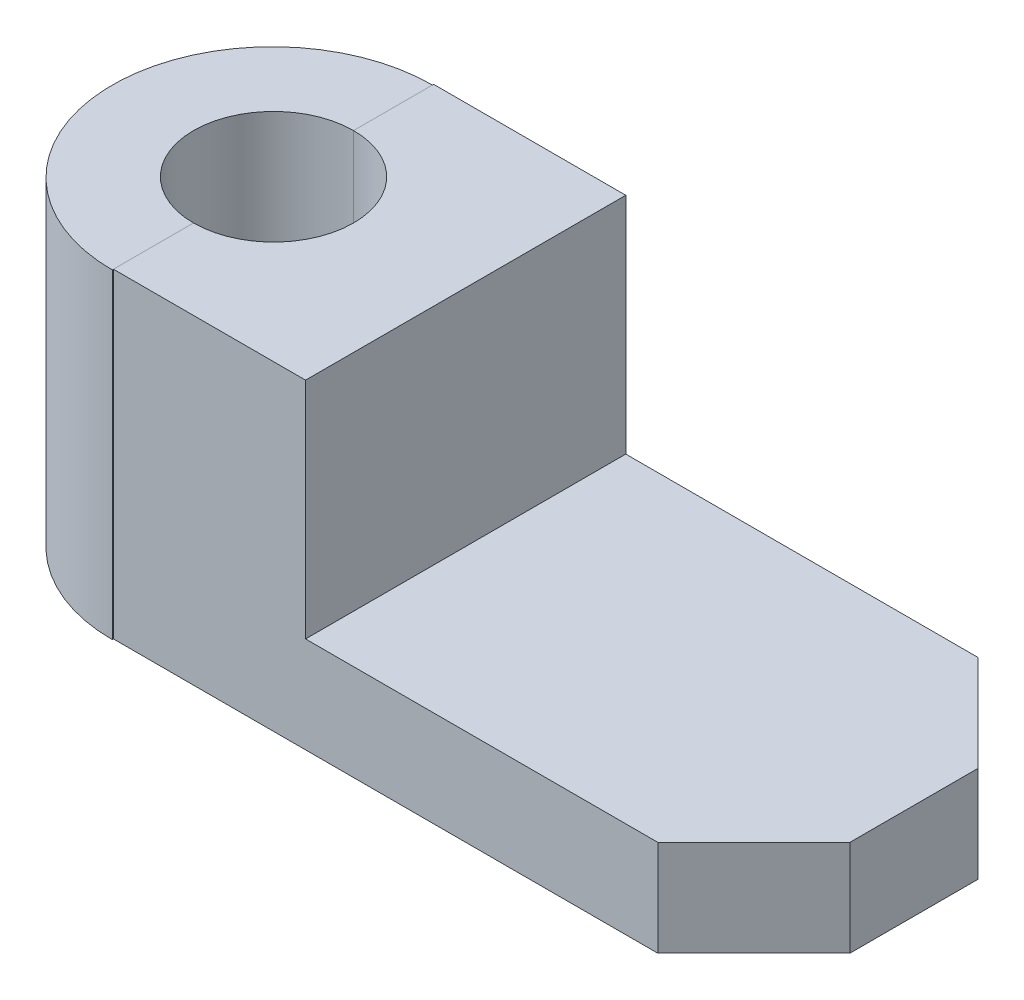
SolidWorks part; units mm, degrees
ref_plane "Front Plane" through (0, 0, 0) normal (0, 0, 1) x (1, 0, 0)
ref_plane "Top Plane" through (0, 0, 0) normal (0, 1, 0) x (1, 0, 0)
ref_plane "Right Plane" through (0, 0, 0) normal (1, 0, 0) x (0, 0, -1)
sketch "Sketch1" plane through (0, 0, 0) normal (0, 0, 1) x (1, 0, 0)
  line L0 (-18, 30) -> (0, 30)
  line L1 (0, 30) -> (0, 9)
  line L2 (0, 9) -> (42, 9)
  line L3 (42, 9) -> (42, 0)
  line L4 (42, 0) -> (0, 0)
  line L5 (0, 0) -> (-18, 0)
  line L6 (-18, 0) -> (-18, 30)
  dimension "D1" = 18
  dimension "D2" = 60
  dimension "D3" = 30
  dimension "D4" = 9
extrude "Boss-Extrude1" add sketch "Sketch1" against normal blind 15 and the other way blind 15
sketch "Sketch2" plane through (0, 30, 0) normal (0, 1, 0) x (1, 0, 0)
  line L0 (-18, 15) -> (-18, -15) construction
  line L1 (-18, 14.8899) -> (-18, -15.1101)
  arc A0 (-18, 14.8899) -> (-18, -15.1101) centre (-18, -0.1101) ccw
  point P3 (0, 0)
  point P6 (-18, -0.1101)
  dimension "D2" = 15
  dimension "D1" = 30
extrude "Boss-Extrude2" add sketch "Sketch2" against normal blind 30
sketch "Sketch3" plane through (0, 30, 0) normal (0, 1, 0) x (1, 0, 0)
  line L0 (0, 15) -> (-18, 15) construction
  line L1 (0, 15) -> (0, -15) construction
  circle A0 centre (-18, 0) radius 7.5
  circle A1 centre (-18, 0) radius 7.5
  dimension "D1" = 15
  dimension "D2" = 15
  dimension "D3" = 18
chamfer "Chamfer1" distance 9 angle 45 1 edges at (42, 4.5, 15)
chamfer "Chamfer2" distance 9 angle 45 1 edges at (42, 4.5, -15)
extrude "Cut-Extrude2" cut sketch "Sketch3" against normal through all contours A0
sketch3d "3DSketch2"
  line L0 (0, 30, 0.2026) -> (42, 9, 0)
  line L1 (0, 30, 15) -> (0, 30, -15) construction
  line L2 (42, 9, 6) -> (42, 9, -6) construction
  point P6 (0, 0, 0)
